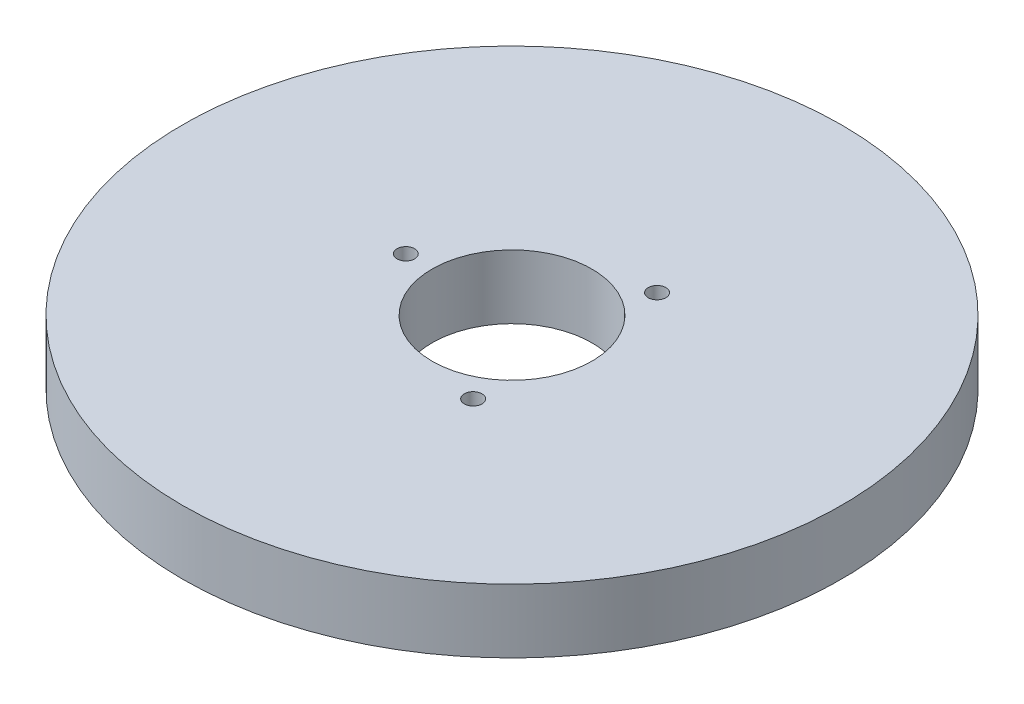
SolidWorks part; units mm, degrees
ref_plane "Front Plane" through (0, 0, 0) normal (0, 0, 1) x (1, 0, 0)
ref_plane "Top Plane" through (0, 0, 0) normal (0, 1, 0) x (1, 0, 0)
ref_plane "Right Plane" through (0, 0, 0) normal (1, 0, 0) x (0, 0, -1)
sketch "Sketch1" plane through (0, 0, 0) normal (0, 1, 0) x (1, 0, 0)
  circle A0 centre (0, 0) radius 82.5
  dimension "FLANGE_OD" = 165
extrude "Boss-Extrude1" add sketch "Sketch1" along normal blind 16
sketch "Sketch2" plane through (0, 0, 0) normal (0, 1, 0) x (1, 0, 0)
  circle A0 centre (0, 0) radius 20
  dimension "BORE_D" = 40
extrude "Cut-Extrude1" cut sketch "Sketch2" along normal through all
sketch "Sketch3" plane through (0, 16, 0) normal (0, 1, 0) x (1, 0, 0)
  circle A0 centre (0, 0) radius 26.5843 construction
  circle A1 centre (-26.5843, 0) radius 2.2087
  dimension "BOLT_D" = 4.4175
  dimension "BOLT_PCD" = 53.1685
extrude "Cut-Extrude2" cut sketch "Sketch3" against normal blind 10.3569
pattern_circular "CirPattern1" count 3 over 360 about axis through (0, 0, 0) along (0, 1, 0) of "Cut-Extrude2"
